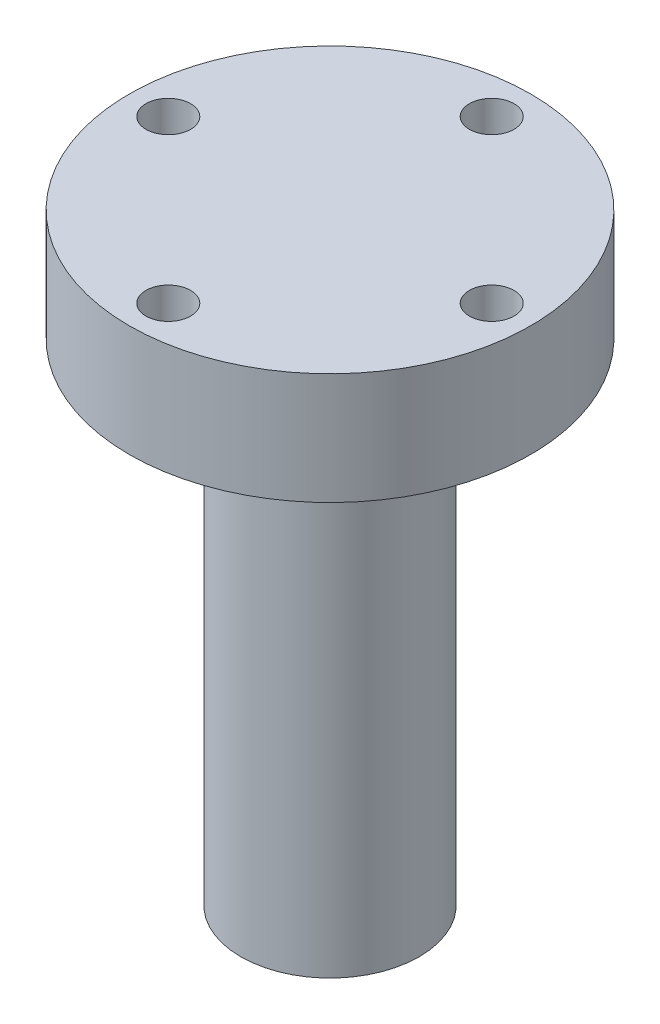
SolidWorks part; units mm, degrees
ref_plane "Front Plane" through (0, 0, 0) normal (0, 0, 1) x (1, 0, 0)
ref_plane "Top Plane" through (0, 0, 0) normal (0, 1, 0) x (1, 0, 0)
ref_plane "Right Plane" through (0, 0, 0) normal (1, 0, 0) x (0, 0, -1)
sketch "Sketch1" plane through (0, 0, 0) normal (0, 1, 0) x (1, 0, 0)
  circle A0 centre (0, 0) radius 9
  dimension "D1" = 18
extrude "BracketMount" add sketch "Sketch1" along normal blind 5
sketch "Sketch2" plane through (0, 5, 0) normal (0, 1, 0) x (1, 0, 0)
  circle A0 centre (0, 7.25) radius 1
  circle A7 centre (7.25, 0) radius 1
  circle A8 centre (0, -7.25) radius 1
  circle A9 centre (-7.25, 0) radius 1
  point P19 (0, 0)
  dimension "D1" = 2
  dimension "D3" = 7.25
  dimension "D2" = 4
extrude "Bracket-MountHoles" cut sketch "Sketch2" against normal up to surface (5 mm away) up to face at (0, 0, 9)
sketch "Sketch3" plane through (0, 0, 0) normal (0, -1, 0) x (1, 0, 0)
  circle A0 centre (0, 0) radius 4
  dimension "D1" = 8
extrude "StepperSleeve" add sketch "Sketch3" along normal blind 22
sketch "Sketch5" plane through (0, -22, 0) normal (0, -1, 0) x (1, 0, 0)
  line L3 (1.94, 1.5926) -> (1.94, -1.5926)
  circle A0 centre (0, 0) radius 4 construction
  arc A6 (1.94, 1.5926) -> (1.94, -1.5926) centre (0, 0) ccw
  point P1 (0, 0)
  point P7 (-2.51, 0)
  dimension "D2" = 2.51
  dimension "D1" = 4.45
extrude "OrientationNub" cut sketch "Sketch5" against normal up to surface (22 mm away) up to face at (0, 0, 4)
